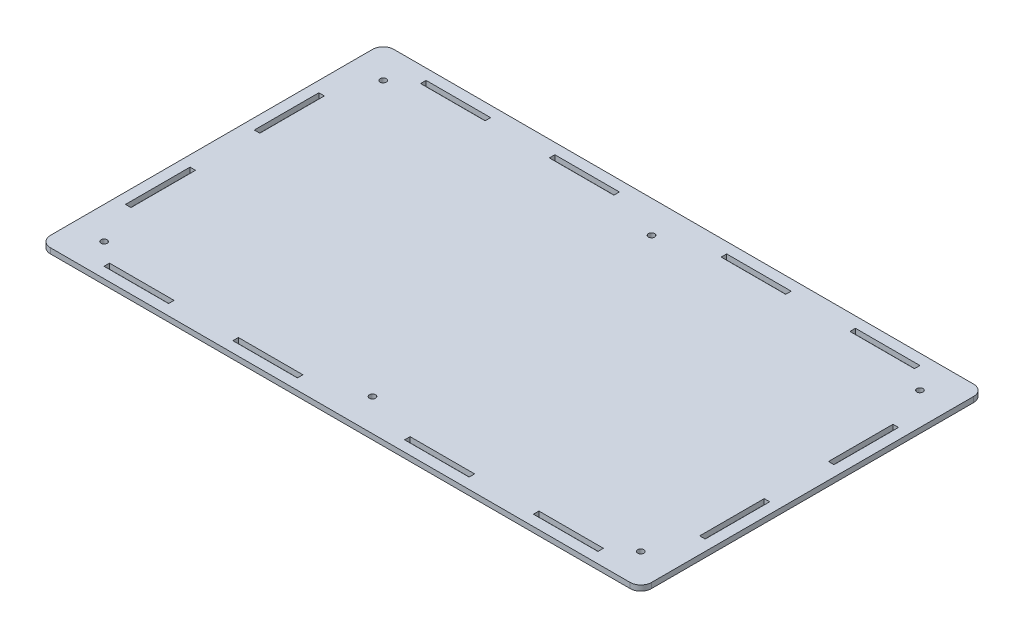
SolidWorks part; units mm, degrees
ref_plane "Front Plane" through (0, 0, 0) normal (0, 0, 1) x (1, 0, 0)
ref_plane "Top Plane" through (0, 0, 0) normal (0, 1, 0) x (1, 0, 0)
ref_plane "Right Plane" through (0, 0, 0) normal (1, 0, 0) x (0, 0, -1)
ref_axis "Axis1" through (0, 0, -135.9953) along (0, 0, 1)
sketch "Panel Profile" plane through (0, 0, 0) normal (0, 1, 0) x (1, 0, 0)
  line L1 (-177.8, 101.6) -> (177.8, 101.6)
  line L2 (-177.8, 101.6) -> (-177.8, -101.6)
  line L3 (-177.8, -101.6) -> (177.8, -101.6)
  line L4 (177.8, 101.6) -> (177.8, -101.6)
  line L5 (-177.8, 101.6) -> (177.8, -101.6) construction
  line L6 (-177.8, -101.6) -> (177.8, 101.6) construction
  point P0 (0, 0)
  dimension "D1" = 203.2
  dimension "D2" = 355.6
sketch "Right Hand Buttons" plane through (0, 0, 0) normal (0, 1, 0) x (1, 0, 0)
  line L0 (85, 70.6) -> (113.8, 70.6) construction
  line L5 (-55, 0) -> (55, 0) construction
  line L6 (0, -55) -> (0, 55) construction
  line L7 (60, 56.2) -> (60, 25) construction
  line L8 (85, 70.6) -> (85, 39.4) construction
  line L9 (113.8, 70.6) -> (113.8, 39.4) construction
  line L10 (142.6, 63.4) -> (142.6, 32.2) construction
  circle A0 centre (60, 56.2) radius 12
  circle A1 centre (85, 70.6) radius 12
  circle A2 centre (113.8, 70.6) radius 12
  circle A7 centre (142.6, 63.4) radius 12
  circle A8 centre (60, 25) radius 12
  circle A9 centre (85, 39.4) radius 12
  circle A10 centre (113.8, 39.4) radius 12
  circle A11 centre (142.6, 32.2) radius 12
  point P0 (0, 0)
  dimension "D2" = 24
  dimension "D1" = 25
  dimension "D3" = 28.8
  dimension "D4" = 14.4
  dimension "D5" = 25
  dimension "D6" = 28.8
  dimension "D7" = 7.2
  dimension "D8" = 31.2
  dimension "D9" = 60
extrude "Panel-Profile" add sketch "Panel Profile" against normal blind 3.175
extrude "Right Buttons" [suppressed] cut sketch "Right Hand Buttons" against normal blind 3.175 and the other way through all
sketch "Sketch4" [suppressed] plane through (0, 0, 0) normal (0, 1, 0) x (1, 0, 0)
  line L0 (28.0585, -29.4) -> (28.0585, -58.2) construction
  line L1 (53, -15) -> (53, -43.8) construction
  line L2 (28.0585, -29.4) -> (53, -15) construction
  line L3 (28.0585, -29.4) -> (53, -43.8) construction
  line L4 (53, -15) -> (77.9415, -29.4) construction
  line L5 (53, -43.8) -> (77.9415, -29.4) construction
  line L6 (28.0585, -58.2) -> (53, -43.8) construction
  circle A0 centre (53, -43.8) radius 12
  circle A1 centre (53, -15) radius 12
  circle A2 centre (77.9415, -29.4) radius 12
  circle A3 centre (28.0585, -29.4) radius 12
  circle A4 centre (28.0585, -58.2) radius 12
  circle A5 centre (60, 25) radius 12 construction
  dimension "D1" = 24
  dimension "D3" = 40
  dimension "D4" = 7
  dimension "D2" = 28.8
extrude "C-Stick" [suppressed] cut sketch "Sketch4" against normal blind 3.175
sketch "Start Button" plane through (0, 0, 0) normal (0, 1, 0) x (1, 0, 0)
  line L0 (0, -1.7463) -> (0, 1.7463) construction
  line L1 (177.8, 101.6) -> (-177.8, 101.6) construction
  circle A0 centre (0, 56.6) radius 12
  dimension "D1" = 24
  dimension "D2" = 45
extrude "Start" [suppressed] cut sketch "Start Button" against normal blind 3.175 contours A0
sketch "Sketch7" [suppressed] plane through (0, 0, 0) normal (0, 1, 0) x (1, 0, 0)
  line L0 (0, -55) -> (0, 55) construction
  circle A0 centre (142.6, 32.2) radius 12 construction
  circle A1 centre (113.8, 39.4) radius 12 construction
  circle A2 centre (85, 39.4) radius 12 construction
  circle A3 centre (60, 25) radius 12 construction
  circle A4 centre (142.6, 32.2) radius 12 construction
  circle A5 centre (113.8, 39.4) radius 12 construction
  circle A6 centre (85, 39.4) radius 12 construction
  circle A7 centre (60, 25) radius 12 construction
  circle A8 centre (-142.6, 32.2) radius 12
  circle A9 centre (-113.8, 39.4) radius 12
  circle A10 centre (-85, 39.4) radius 12
  circle A11 centre (-60, 25) radius 12
  circle A12 centre (28.0585, -58.2) radius 12 construction
  circle A13 centre (53, -43.8) radius 12 construction
  circle A14 centre (28.0585, -58.2) radius 12 construction
  circle A15 centre (53, -43.8) radius 12 construction
  circle A16 centre (-53, -43.8) radius 12
  circle A17 centre (-28.0585, -58.2) radius 12
extrude "L-Stick" [suppressed] cut sketch "Sketch7" against normal blind 3.175
sketch "Sketch8" plane through (0, 0, 0) normal (0, 1, 0) x (1, 0, 0)
  line L0 (0, 135.9953) -> (0, -135.9953) construction
  line L1 (177.8, 101.6) -> (-177.8, 101.6) construction
  line L2 (-177.8, 101.6) -> (-177.8, -101.6) construction
  line L3 (-177.8, -101.6) -> (177.8, -101.6) construction
  line L4 (177.8, -101.6) -> (177.8, 101.6) construction
  circle A0 centre (-158.75, 82.55) radius 1.8288
  circle A1 centre (0, 82.55) radius 1.8288
  circle A2 centre (158.75, 82.55) radius 1.8288
  circle A3 centre (-158.75, -82.55) radius 1.8288
  circle A4 centre (0, -82.55) radius 1.8288
  circle A5 centre (158.75, -82.55) radius 1.8288
  dimension "D1" = 3.6576
  dimension "D2" = 19.05
  dimension "D3" = 19.05
  dimension "D4" = 19.05
  dimension "D5" = 19.05
extrude "Cut-Extrude1" cut sketch "Sketch8" against normal blind 10
fillet "Fillet1" radius 6.35 4 edges at (177.8, -1.5875, -101.6) (177.8, -1.5875, 101.6) (-177.8, -1.5875, 101.6) (-177.8, -1.5875, -101.6)
sketch "Sketch9" plane through (0, 0, 0) normal (0, 1, 0) x (1, 0, 0)
  line L1 (-146.09, 95.25) -> (-107.91, 95.25)
  line L2 (-146.09, 95.25) -> (-146.09, 92)
  line L3 (-146.09, 92) -> (-107.91, 92)
  line L4 (-107.91, 95.25) -> (-107.91, 92)
  line L5 (-69.89, 95.25) -> (-31.71, 95.25)
  line L6 (-69.89, 95.25) -> (-69.89, 92)
  line L7 (-69.89, 92) -> (-31.71, 92)
  line L8 (-31.71, 95.25) -> (-31.71, 92)
  line L9 (171.45, 101.6) -> (-171.45, 101.6) construction
  line L10 (-127, 95.25) -> (-127, 92) construction
  line L11 (-50.8, 95.25) -> (-50.8, 92) construction
  line L12 (0, -1.7463) -> (0, 1.7463) construction
  dimension "D1" = 3.25
  dimension "D2" = 38.18
  dimension "D3" = 76.2
  dimension "D4" = 50.8
  dimension "D5" = 6.35
extrude "Cut-Extrude2" cut sketch "Sketch9" against normal through all both and the other way through all
mirror "Mirror1" about plane through (0, 0, 0) normal (1, 0, 0) of "Cut-Extrude2"
mirror "Mirror2" about plane through (0, 0, 0) normal (0, 0, 1) of "Mirror1", "Cut-Extrude2"
sketch "Sketch10" plane through (0, 0, 0) normal (0, 1, 0) x (1, 0, 0)
  line L0 (-171.45, 38.1) -> (-168.1988, 38.1) construction
  line L1 (-171.45, 57.1881) -> (-168.1988, 57.1881)
  line L2 (-171.45, 57.1881) -> (-171.45, 19.0119)
  line L3 (-171.45, 19.0119) -> (-168.1988, 19.0119)
  line L4 (-168.1988, 57.1881) -> (-168.1988, 19.0119)
  line L5 (-1.7463, 0) -> (1.7463, 0) construction
  line L6 (-177.8, 95.25) -> (-177.8, -95.25) construction
  dimension "D1" = 3.2512
  dimension "D2" = 38.1762
  dimension "D3" = 38.1
  dimension "D4" = 6.35
extrude "Cut-Extrude3" cut sketch "Sketch10" against normal through all both and the other way through all
mirror "Mirror3" about plane through (0, 0, 0) normal (0, 0, 1) of "Cut-Extrude3"
mirror "Mirror4" about plane through (0, 0, 0) normal (1, 0, 0) of "Cut-Extrude3", "Mirror3"
sketch "Sketch12" plane through (0, -3.175, 0) normal (0, -1, 0) x (1, 0, 0)
  line L0 (-168.1988, 19.0119) -> (-168.1988, 57.1881) construction
  line L1 (-65.5988, 41.6) -> (-167.1988, 41.6) construction
  line L2 (-65.5988, 41.6) -> (-65.5988, -11.74) construction
  line L3 (-65.5988, -11.74) -> (-167.1988, -11.74) construction
  line L4 (-167.1988, 41.6) -> (-167.1988, -11.74) construction
  line L5 (-171.45, 101.6) -> (171.45, 101.6) construction
  circle A0 centre (-79.5688, 39.06) radius 1.4732
  circle A1 centre (-131.6388, 6.04) radius 1.4732
  circle A2 centre (-162.1188, 39.06) radius 1.4732
  dimension "D3" = 2.9464
  dimension "D8" = 96.52
  dimension "D1" = 101.6
  dimension "D2" = 53.34
  dimension "D4" = 13.97
  dimension "D5" = 2.54
  dimension "D6" = 66.04
  dimension "D7" = 35.56
  dimension "D9" = 2.54
  dimension "D10" = 1
  dimension "D11" = 60
extrude "Cut-Extrude4" [suppressed] cut sketch "Sketch12" against normal through all both and the other way through all
equation "\"button_diam\"= 24mm'Button Diameter"
equation "\"x_spacing\"= 0'Horizonal Button Spacing"
equation "\"y_spacing\"= 0'Vertical Button Spacing"
equation "\"slant\"= 0'Difference between Top and Buttom Row"
equation "\"teeth\"= 1.5in'Teeth Size for Box"
equation "\"teeth_tol\"= 0.003in'Tolerance of Meshing Teeth"
equation "\"t\"= 0.125in'Sheet Thickness"
equation "\"D1@Sketch10\"=\"t\"+\"teeth_tol\""
equation "\"D2@Sketch10\"=\"teeth\"+\"teeth_tol\""
equation "\"hole_offset\"= 0.75in'Distance from Edge to Mounting Holes"
equation "\"D2@Sketch8\"=\"hole_offset\""
equation "\"D3@Sketch8\"=\"hole_offset\""
equation "\"D4@Sketch8\"=\"hole_offset\""
equation "\"D5@Sketch8\"=\"hole_offset\""
